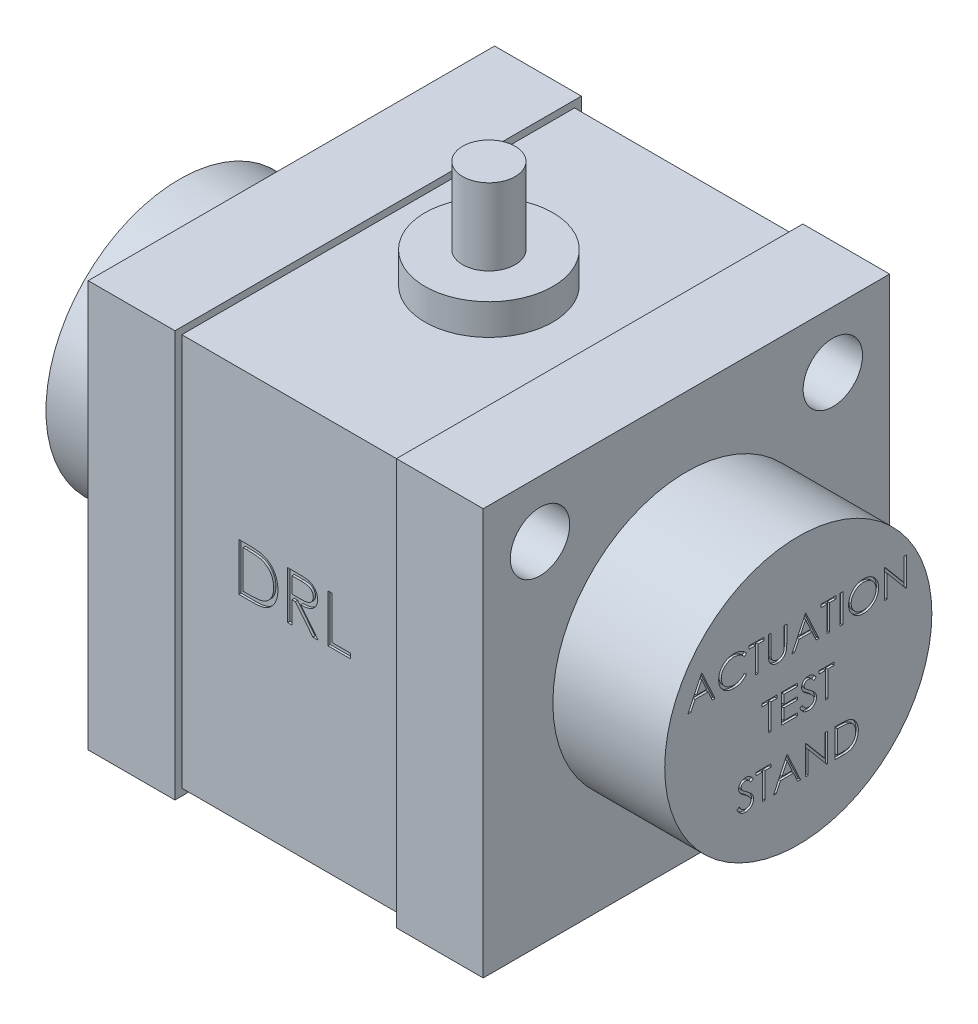
SolidWorks part; units mm, degrees
ref_plane "Front Plane" through (0, 0, 0) normal (0, 0, 1) x (1, 0, 0)
ref_plane "Top Plane" through (0, 0, 0) normal (0, 1, 0) x (1, 0, 0)
ref_plane "Right Plane" through (0, 0, 0) normal (1, 0, 0) x (0, 0, -1)
sketch "Sketch4" plane through (0, 0, 0) normal (1, 0, 0) x (0, 0, -1)
  line L0 (-21.844, 21.844) -> (21.844, 21.844)
  line L1 (-22.606, -22.606) -> (22.606, -22.606)
  line L2 (-22.606, -22.606) -> (-22.606, 22.606)
  line L3 (-22.606, 22.606) -> (22.606, 22.606)
  line L4 (22.606, -22.606) -> (22.606, 22.606)
  line L5 (-22.606, -22.606) -> (22.606, 22.606) construction
  line L6 (-22.606, 22.606) -> (22.606, -22.606) construction
  line L7 (21.844, -21.844) -> (21.844, 21.844)
  line L8 (-21.844, -21.844) -> (21.844, -21.844)
  line L9 (-21.844, -21.844) -> (-21.844, 21.844)
  point P0 (0, 0)
  dimension "D1" = 45.212
  dimension "D2" = 45.212
  dimension "D3" = 0.762
extrude "Boss-Extrude1" add sketch "Sketch4" against normal blind 9.652 contours L9 L8 L7 L0 | L1 L4 L3 L2 L8 L9 L0 L7 | L0 L7 L8 L9 | L2 L1 L4 L3 region at (0, 0, 0) region at (0, 0, 21.9666)
extrude "Boss-Extrude2" add sketch "Sketch4<3>" along normal blind 24.638 contours L9 L8 L7 L0 region at (0, 0, 0)
sketch "Sketch4<3>" plane through (0, 0, 0) normal (1, 0, 0) x (0, 0, -1) same geometry as "Sketch4"
extrude "Boss-Extrude3" add sketch "Sketch4<4>" along normal blind 9.652 from surface contours L9 L8 L7 L0 | L1 L4 L3 L2 L8 L9 L0 L7 region at (0, 0, 0) region at (0, 0, 21.9666) starting at face at (24.638, 0, 0)
sketch "Sketch4<4>" plane through (0, 0, 0) normal (1, 0, 0) x (0, 0, -1) same geometry as "Sketch4"
sketch "Sketch5" plane through (0, 21.844, 0) normal (0, 1, 0) x (1, 0, 0)
  line L0 (12.319, 21.844) -> (12.319, -21.844) construction
  line L1 (24.638, 21.844) -> (0, 21.844) construction
  line L2 (24.638, -21.844) -> (0, -21.844) construction
  circle A0 centre (12.319, 0) radius 7.112
  circle A1 centre (12.319, 0) radius 2.921
  dimension "D1" = 14.224
  dimension "D2" = 5.842
extrude "Boss-Extrude4" add sketch "Sketch5" along normal blind 3.4379 contours A0 L0 A1 | L0 A0 A1 | A1 L0 | L0 A1 | A1 | A0 region at (15.6984, 21.844, 0) region at (8.9396, 21.844, 0) region at (13.5587, 21.844, 0) region at (11.0793, 21.844, 0)
extrude "Boss-Extrude5" add sketch "Sketch5<3>" along normal blind 8.4963 from surface contours L0 A1 | A1 L0 region at (13.5587, 21.844, 0) region at (11.0793, 21.844, 0) starting at face at (12.319, 25.2819, 7.112)
sketch "Sketch5<3>" plane through (0, 21.844, 0) normal (0, 1, 0) x (1, 0, 0) same geometry as "Sketch5"
sketch "Sketch6" plane through (34.29, 0, 0) normal (1, 0, 0) x (0, 0, -1)
  line L0 (-22.606, 22.606) -> (-22.606, -22.606) construction
  line L1 (22.606, 22.606) -> (-22.606, 22.606) construction
  line L2 (0, 22.606) -> (0, -22.606) construction
  line L3 (22.606, -22.606) -> (-22.606, -22.606) construction
  circle A0 centre (-16.2865, 16.2865) radius 3.302
  circle A1 centre (16.2865, 16.2865) radius 3.302
  dimension "D3" = 6.604
  dimension "D1" = 6.3195
  dimension "D2" = 6.3195
extrude "Cut-Extrude1" cut sketch "Sketch6" against normal through all
sketch "Sketch7" plane through (34.29, 0, 0) normal (1, 0, 0) x (0, 0, -1)
  circle A0 centre (0, 0) radius 14.859
  dimension "D1" = 29.718
extrude "Boss-Extrude6" add sketch "Sketch7" along normal blind 12.446
extrude "Boss-Extrude7" add sketch "Sketch7<2>" against normal blind 12.446 from surface starting at face at (-9.652, 16.2865, 12.9845)
sketch "Sketch7<2>" plane through (34.29, 0, 0) normal (1, 0, 0) x (0, 0, -1) same geometry as "Sketch7"
sketch "Sketch8" plane through (46.736, 0, 0) normal (1, 0, 0) x (0, 0, -1)
  line L0 (-14.3429, 3.8823) -> (14.3429, 3.8823) construction
  line L1 (0, 14.859) -> (0, -14.859) construction
  circle A0 centre (0, 0) radius 14.859 construction
  circle A1 centre (0, 0) radius 14.859 construction
  text T0 "ACTUATION\r\nTEST\r\nSTAND"
  point P10 (-14.0905, 4.7168)
  point P11 (14.1136, 4.6473)
extrude "Cut-Extrude2" cut sketch "Sketch8" against normal blind 0.254
sketch "Sketch9" plane through (-22.098, 0, 0) normal (-1, 0, 0) x (0, 0, 1)
  line L0 (0, 14.859) -> (0, -14.859) construction
  line L1 (-13.8383, 5.4122) -> (13.8383, 5.4122) construction
  circle A1 centre (0, 0) radius 14.859
  circle A2 centre (0, 0) radius 14.859 construction
  text T0 "IAN'S\r\nA \r\nNERD"
  dimension "D1" = 0
extrude "Cut-Extrude3" cut sketch "Sketch9" against normal blind 0.254
sketch "Sketch10" plane through (0, 0, 21.844) normal (0, 0, 1) x (1, 0, 0)
  line L0 (0, 0) -> (24.638, 0) construction
  line L1 (24.638, 22.606) -> (24.638, -22.606) construction
  text T0 "DRL" font "Century Gothic" height in points 20
extrude "Cut-Extrude4" cut sketch "Sketch10" against normal blind 0.254
sketch "Sketch11" plane through (0, 0, -21.844) normal (0, 0, -1) x (-1, 0, 0)
  line L0 (0, 0) -> (-24.638, 0) construction
  line L1 (-24.638, -21.844) -> (-24.638, 21.844) construction
  text T0 "DRL" font "Century Gothic" height in points 20
extrude "Cut-Extrude5" cut sketch "Sketch11" against normal blind 0.254
